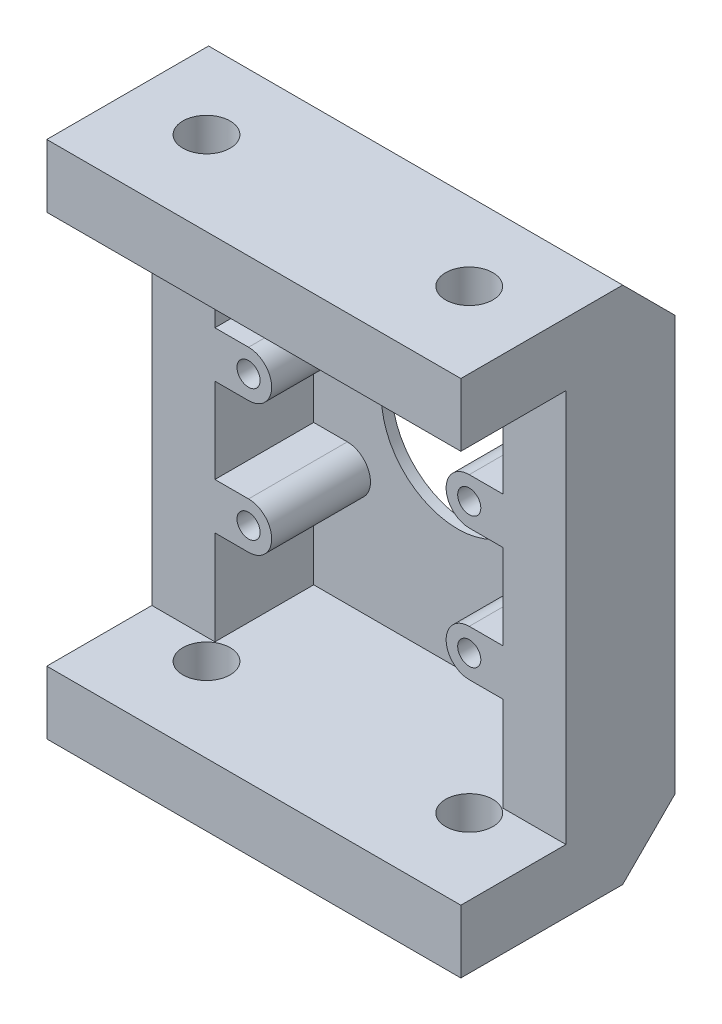
SolidWorks part; units mm, degrees
ref_plane "Front Plane" through (0, 0, 0) normal (0, 0, 1) x (1, 0, 0)
ref_plane "Top Plane" through (0, 0, 0) normal (0, 1, 0) x (1, 0, 0)
ref_plane "Right Plane" through (0, 0, 0) normal (1, 0, 0) x (0, 0, -1)
sketch "Sketch1" plane through (0, 0, 0) normal (0, 0, 1) x (1, 0, 0)
  line L0 (-19.7, -24.7) -> (-19.7, 24.7)
  line L1 (20, -25) -> (-20, -25) construction
  line L2 (20, -25) -> (20, 25) construction
  line L3 (20, 25) -> (-20, 25) construction
  line L4 (-20, -25) -> (-20, 25) construction
  line L5 (20, -25) -> (-20, 25) construction
  line L6 (20, 25) -> (-20, -25) construction
  line L7 (19.7, 24.7) -> (-19.7, 24.7)
  line L8 (19.7, -24.7) -> (19.7, 24.7)
  line L9 (19.7, -24.7) -> (-19.7, -24.7)
  point P0 (0, 0)
  dimension "D1" = 50
  dimension "D2" = 40
  dimension "D3" = 0.3
extrude "Boss-Extrude1" add sketch "Sketch1" along normal blind 1
sketch "Sketch2" plane through (0, 0, 1) normal (0, 0, 1) x (1, 0, 0)
  circle A0 centre (0, 0) radius 7.25
  dimension "D1" = 14.5
extrude "Cut-Extrude1" cut sketch "Sketch2" against normal through all
sketch "Sketch3" plane through (0, 0, 1) normal (0, 0, 1) x (1, 0, 0)
  line L0 (10.5, 4.98) -> (10.5, 0) construction
  line L1 (10.5, 0) -> (0, 0) construction
  line L2 (-10.5, 4.98) -> (-10.5, 0) construction
  line L3 (-10.5, 0) -> (0, 0) construction
  line L4 (-10.5, 0) -> (-10.5, -7.52) construction
  line L5 (10.5, 0) -> (10.5, -7.52) construction
  circle A0 centre (-10.5, 4.98) radius 1
  circle A1 centre (10.5, 4.98) radius 1
  circle A2 centre (-10.5, -7.52) radius 1
  circle A3 centre (10.5, -7.52) radius 1
  circle A4 centre (-10.5, 4.98) radius 2.2
  circle A5 centre (-10.5, -7.52) radius 2.2
  circle A6 centre (10.5, -7.52) radius 2.2
  circle A7 centre (10.5, 4.98) radius 2.2
  dimension "D4" = 2
  dimension "D5" = 1.2
  dimension "D1" = 10.5
  dimension "D2" = 4.98
  dimension "D3" = 7.52
extrude "Boss-Extrude2" add sketch "Sketch3" along normal blind 10.4 from surface starting at face at (7.25, 0, 0)
sketch "Sketch4" plane through (0, 0, 1) normal (0, 0, 1) x (1, 0, 0)
  line L0 (19.7, -24.7) -> (19.7, 24.7) construction
  line L1 (-19.7, -24.7) -> (19.7, -24.7) construction
  line L2 (19.7, 24.7) -> (-19.7, 24.7) construction
  line L3 (-19.7, 24.7) -> (-19.7, -24.7) construction
  line L4 (19.7, -24.7) -> (19.7, 24.7)
  line L5 (-19.7, -24.7) -> (19.7, -24.7)
  line L6 (19.7, 24.7) -> (-19.7, 24.7)
  line L7 (-19.7, 24.7) -> (-19.7, -24.7)
  line L8 (-13.7, 18.7) -> (-13.7, -18.7)
  line L9 (-13.7, -18.7) -> (13.7, -18.7)
  line L10 (13.7, -18.7) -> (13.7, 18.7)
  line L11 (13.7, 18.7) -> (-13.7, 18.7)
  dimension "D1" = 6
extrude "Boss-Extrude4" add sketch "Sketch4" along normal up to surface (9.4 mm away) up to face at (-11.5, 4.98, 10.4)
sketch "Sketch5" plane through (0, 0, 10.4) normal (0, 0, 1) x (1, 0, 0)
  line L0 (19.7, 24.7) -> (19.7, -24.7) construction
  line L1 (-19.7, 24.7) -> (19.7, 24.7)
  line L2 (-19.7, 24.7) -> (-19.7, 18.7)
  line L3 (-19.7, 18.7) -> (19.7, 18.7)
  line L4 (19.7, 24.7) -> (19.7, 18.7)
  line L5 (-19.7, -24.7) -> (-19.7, 24.7) construction
  line L6 (19.7, -24.7) -> (-19.7, -24.7)
  line L7 (19.7, -24.7) -> (19.7, -18.7)
  line L8 (19.7, -18.7) -> (-19.7, -18.7)
  line L9 (-19.7, -24.7) -> (-19.7, -18.7)
  line L10 (-13.7, 18.7) -> (13.7, 18.7) construction
  line L11 (-13.7, -18.7) -> (13.7, -18.7) construction
extrude "Boss-Extrude5" add sketch "Sketch5" along normal blind 10
sketch "Sketch6" plane through (0, 24.7, 0) normal (0, 1, 0) x (1, 0, 0)
  circle A0 centre (-12.5, -12.4) radius 1.65 construction
  circle A1 centre (12.5, -12.4) radius 1.65 construction
  circle A2 centre (-12.5, -12.4) radius 1.65
  circle A3 centre (12.5, -12.4) radius 1.65
extrude "Cut-Extrude3" cut sketch "Sketch6" against normal through all
sketch "Sketch7" plane through (0, 24.7, 0) normal (0, 1, 0) x (1, 0, 0)
  circle A0 centre (12.5, -12.4) radius 2.25
  circle A1 centre (-12.5, -12.4) radius 2.25
  dimension "D1" = 4.5
extrude "Cut-Extrude4" cut sketch "Sketch7" against normal through all
sketch "Sketch8" plane through (0, 0, 10.4) normal (0, 0, 1) x (1, 0, 0)
  line L0 (-10.5, 7.18) -> (-13.7, 7.18)
  line L1 (-13.7, -18.7) -> (-13.7, 18.7) construction
  line L2 (-10.5, 2.78) -> (-13.7, 2.78)
  line L3 (-13.7, 18.7) -> (-13.7, -18.7) construction
  line L4 (-10.5, -5.32) -> (-13.7, -5.32)
  line L5 (10.5, 7.18) -> (13.7, 7.18)
  line L6 (13.7, -18.7) -> (13.7, 18.7) construction
  line L7 (13.7, 7.18) -> (13.7, 2.78)
  line L8 (13.7, 2.78) -> (10.5, 2.78)
  line L9 (-10.5, -9.72) -> (-13.7, -9.72)
  line L10 (-13.7, -9.72) -> (-13.7, -5.32)
  line L11 (10.5, -5.32) -> (13.7, -5.32)
  line L12 (13.7, -5.32) -> (13.7, -9.72)
  line L13 (13.7, -9.72) -> (10.5, -9.72)
  line L14 (-13.7, 7.18) -> (-13.7, 2.78)
  arc A0 (-11.4692, 3.005) -> (-11.4692, 6.955) centre (-10.5, 4.98) ccw construction
  circle A1 centre (-10.5, 4.98) radius 2.2 construction
  arc A2 (-11.4692, -9.495) -> (-11.4692, -5.545) centre (-10.5, -7.52) ccw construction
  circle A3 centre (-10.5, -7.52) radius 2.2 construction
  circle A4 centre (10.5, 4.98) radius 2.2 construction
  arc A5 (11.4692, 6.955) -> (11.4692, 3.005) centre (10.5, 4.98) ccw construction
  arc A7 (11.4692, -5.545) -> (11.4692, -9.495) centre (10.5, -7.52) ccw construction
  circle A8 centre (10.5, -7.52) radius 2.2 construction
  arc A12 (-10.5, 7.18) -> (-10.5, 2.78) centre (-10.5, 4.98) cw
  arc A13 (10.5, 7.18) -> (10.5, 2.78) centre (10.5, 4.98) ccw
  arc A14 (10.5, -5.32) -> (10.5, -9.72) centre (10.5, -7.52) ccw
  arc A15 (-10.5, -5.32) -> (-10.5, -9.72) centre (-10.5, -7.52) cw
extrude "Boss-Extrude6" add sketch "Sketch8" against normal up to surface (9.4 mm away) up to face at (0, 0, 1)
sketch "Sketch9" plane through (0, 0, 10.4) normal (0, 0, 1) x (1, 0, 0)
  circle A0 centre (-10.5, 4.98) radius 1.1
  circle A1 centre (10.5, 4.98) radius 1.1
  circle A2 centre (10.5, -7.52) radius 1.1
  circle A3 centre (-10.5, -7.52) radius 1.1
  arc A4 (-10.5, -9.72) -> (-10.5, -5.32) centre (-10.5, -7.52) ccw construction
  arc A5 (-10.5, 2.78) -> (-10.5, 7.18) centre (-10.5, 4.98) ccw construction
  arc A6 (10.5, 7.18) -> (10.5, 2.78) centre (10.5, 4.98) ccw construction
  arc A7 (10.5, -5.32) -> (10.5, -9.72) centre (10.5, -7.52) ccw construction
  dimension "D1" = 2.2
extrude "Cut-Extrude5" cut sketch "Sketch9" against normal blind 8 draft 2
chamfer "Chamfer1" distance 5 angle 45 2 edges at (0, -24.7, 0) (0, 24.7, 0)
